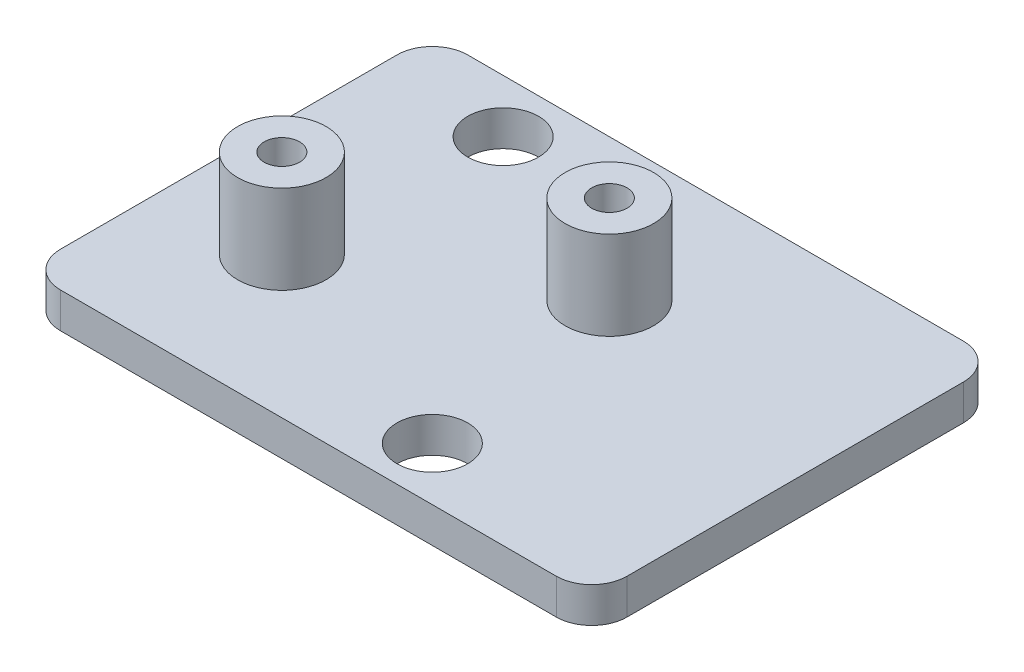
SolidWorks part; units mm, degrees
material "ABS"
ref_plane "Спереди" through (0, 0, 0) normal (0, 0, 1) x (1, 0, 0)
ref_plane "Сверху" through (0, 0, 0) normal (0, 1, 0) x (1, 0, 0)
ref_plane "Справа" through (0, 0, 0) normal (1, 0, 0) x (0, 0, -1)
sketch "Эскиз1" plane through (0, 0, 0) normal (0, 1, 0) x (1, 0, 0)
  line L1 (0, 0) -> (32, 0)
  line L2 (0, 0) -> (0, -23)
  line L3 (0, -23) -> (32, -23)
  line L4 (32, 0) -> (32, -23)
  dimension "D1" = 32
  dimension "D2" = 23
extrude "Бобышка-Вытянуть1" add sketch "Эскиз1" along normal blind 2
sketch "Эскиз4" plane through (0, 2, 0) normal (0, 1, 0) x (1, 0, 0)
  line L0 (0, 0) -> (32, 0) construction
  line L1 (0, -23) -> (32, -23) construction
  line L2 (0, 0) -> (0, -23) construction
  line L3 (32, 0) -> (32, -23) construction
  circle A0 centre (18, -8) radius 2.5
  circle A1 centre (6.5, -15) radius 2.5
  dimension "D1" = 8
  dimension "D2" = 8
  dimension "D3" = 6.5
  dimension "D4" = 14
  dimension "D5" = 5
  dimension "D6" = 5
extrude "Бобышка-Вытянуть2" add sketch "Эскиз4" along normal blind 5
sketch "Эскиз5" plane through (0, 7, 0) normal (0, 1, 0) x (1, 0, 0)
  circle A0 centre (6.5, -15) radius 1
  circle A1 centre (18, -8) radius 1
  dimension "D1" = 2
  dimension "D2" = 2
extrude "Вырез-Вытянуть1" cut sketch "Эскиз5" against normal through all
sketch "Эскиз7" plane through (0, 2, 0) normal (0, 1, 0) x (1, 0, 0)
  line L0 (0, 0) -> (32, 0) construction
  line L1 (0, -23) -> (32, -23) construction
  line L2 (32, 0) -> (32, -23) construction
  line L3 (0, 0) -> (0, -23) construction
  circle A0 centre (7, -3) radius 2
  circle A1 centre (20, -20) radius 2
  dimension "D1" = 3
  dimension "D2" = 4
  dimension "D3" = 3
  dimension "D4" = 4
  dimension "D5" = 12
  dimension "D6" = 7
extrude "Вырез-Вытянуть2" cut sketch "Эскиз7" against normal through all
fillet "Скругление1" radius 2 1 edges at (0, 1, 0) type face fillet first side face at (16, 1, 0) second side face at (0, 1, 11.5)
fillet "Скругление2" radius 2 1 edges at (0, 1, 23) type face fillet first side face at (0, 1, 12.5) second side face at (16, 1, 23)
fillet "Скругление3" radius 2 1 edges at (32, 1, 23) type face fillet first side face at (17, 1, 23) second side face at (32, 1, 11.5)
fillet "Скругление4" radius 2 1 edges at (32, 1, 0) type face fillet first side face at (17, 1, 0) second side face at (32, 1, 10.5)
